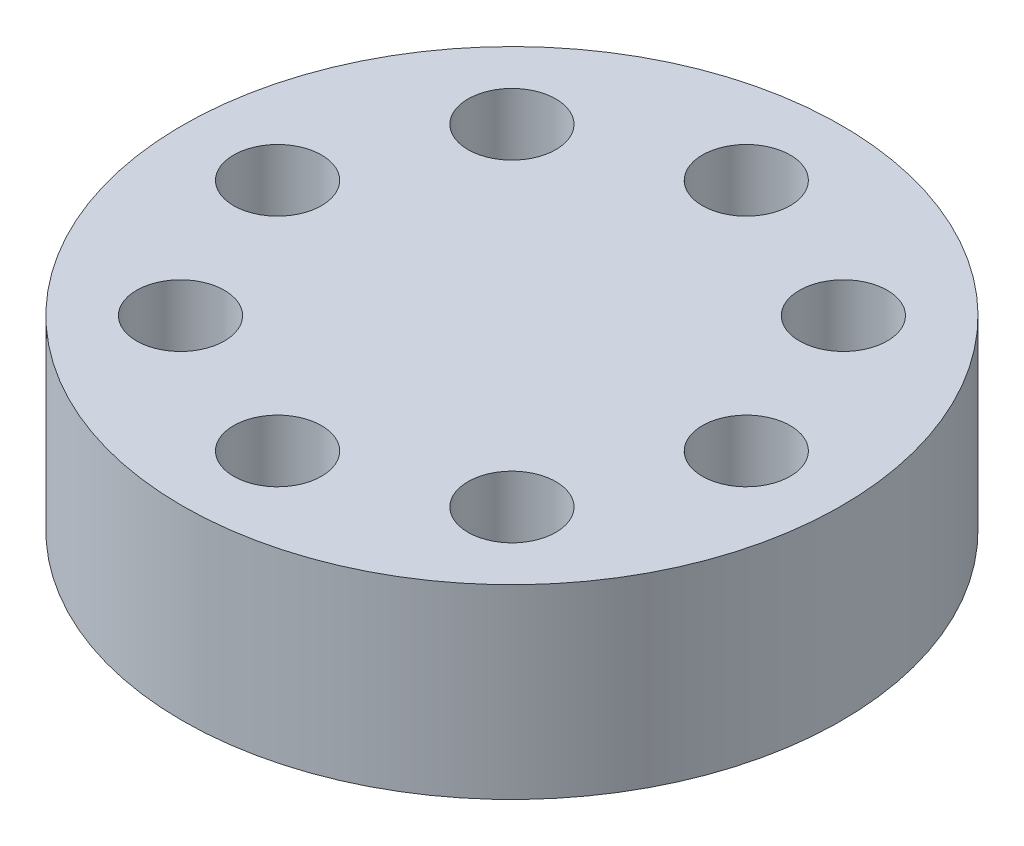
SolidWorks part; units mm, degrees
ref_plane "Front Plane" through (0, 0, 0) normal (0, 0, 1) x (1, 0, 0)
ref_plane "Top Plane" through (0, 0, 0) normal (0, 1, 0) x (1, 0, 0)
ref_plane "Right Plane" through (0, 0, 0) normal (1, 0, 0) x (0, 0, -1)
sketch "Sketch1" plane through (0, 0, 0) normal (0, 1, 0) x (1, 0, 0)
  circle A0 centre (0, 0) radius 22.5
  dimension "D1" = 45
extrude "Boss-Extrude1" add sketch "Sketch1" along normal blind 12.7
sketch "Sketch2" plane through (0, 12.7, 0) normal (0, 1, 0) x (1, 0, 0)
  circle A0 centre (0, 0) radius 16 construction
  circle A1 centre (-16, 0) radius 3
  circle A2 centre (-11.3137, 11.3137) radius 3
  circle A3 centre (0, 16) radius 3
  circle A4 centre (11.3137, 11.3137) radius 3
  circle A5 centre (16, 0) radius 3
  circle A6 centre (11.3137, -11.3137) radius 3
  circle A7 centre (0, -16) radius 3
  circle A8 centre (-11.3137, -11.3137) radius 3
  point P21 (0, 0)
  dimension "D1" = 32
  dimension "D2" = 6
  dimension "D3" = 8
extrude "Cut-Extrude1" cut sketch "Sketch2" against normal through all
equation "\"L1L\"=500"
equation "\"L1Thick\"=6.35"
equation "\"Harm-Drive-Outer\"=74.5"
equation "\"L1-Spacing\"=110"
equation "\"L-Bracket-HoleToWall\"=12.5"
equation "\"L-Bracket-HoleToSide\"=11"
equation "\"Bracket-Hole-D\"=6.8"
equation "\"D1@Boss-Extrude1\"=\"L1Thick\"*2"
